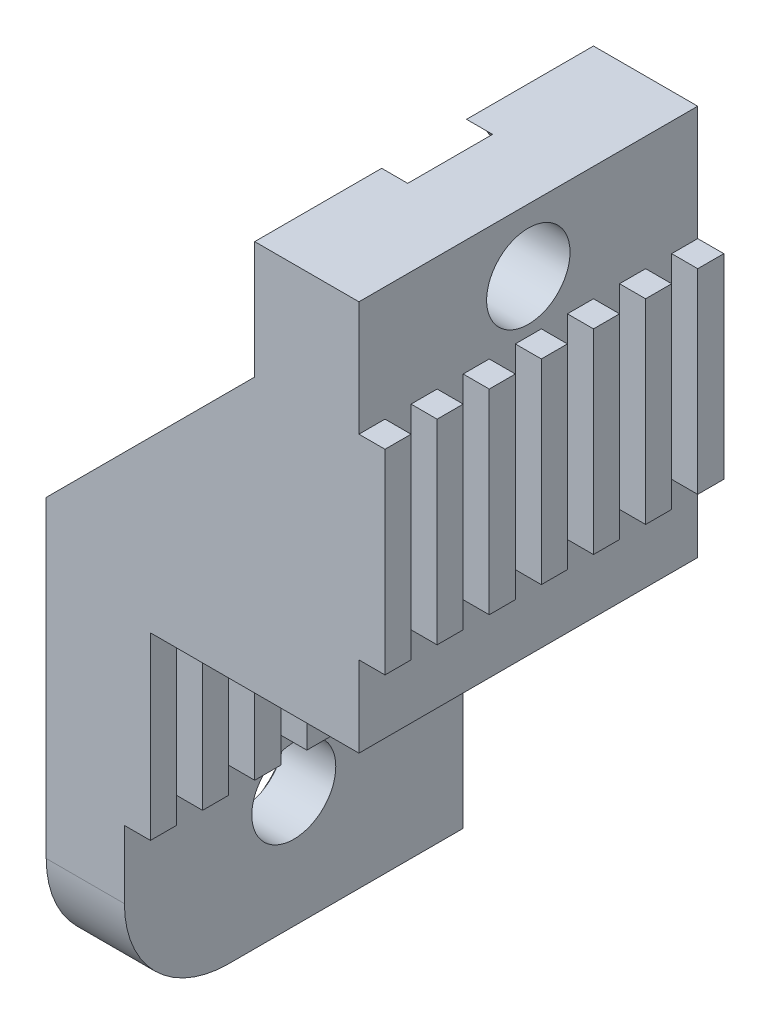
SolidWorks part; units mm, degrees
ref_plane "Front Plane" through (0, 0, 0) normal (0, 0, 1) x (1, 0, 0)
ref_plane "Top Plane" through (0, 0, 0) normal (0, 1, 0) x (1, 0, 0)
ref_plane "Right Plane" through (0, 0, 0) normal (1, 0, 0) x (0, 0, -1)
sketch "Sketch1" plane through (0, 0, 98.1716) normal (0, 0, 1) x (1, 0, 0)
  line L0 (34.2144, 63.2635) -> (28.2644, 63.2635) construction
  line L1 (31.2144, 78.2635) -> (35.2144, 78.2635)
  line L2 (31.2144, 78.2635) -> (31.2144, 63.7635)
  line L4 (35.2144, 78.2635) -> (35.2144, 66.8635)
  line L5 (23.2144, 49.7635) -> (26.2144, 49.7635)
  line L6 (23.2144, 49.7635) -> (23.2144, 63.2635)
  line L8 (26.2144, 49.7635) -> (26.2144, 63.2635)
  line L10 (36.7144, 67.3635) -> (36.7144, 73.8635) construction
  line L12 (31.2144, 63.7635) -> (23.2144, 63.7635)
  line L17 (23.2144, 63.7635) -> (23.2144, 63.2635)
  line L22 (26.2144, 63.2635) -> (35.2144, 63.2635)
  line L24 (35.2144, 66.8635) -> (35.2144, 63.2635)
  dimension "D1" = 14.5
  dimension "D2" = 3
  dimension "D3" = 0
  dimension "D4" = 4
  dimension "D5" = 1.5
  dimension "D6" = 0
  dimension "D7" = 14
  dimension "D8" = 0.5
  dimension "D9" = 5
extrude "Boss-Extrude1" add sketch "Sketch1" against normal blind 13
sketch "Sketch2" plane through (35.2144, 0, 0) normal (1, 0, 0) x (0, 0, -1)
  line L0 (-85.1716, 49.7635) -> (-98.1716, 49.7635) construction
  circle A0 centre (-91.6716, 75.8635) radius 1.6
  circle A1 centre (-91.6716, 54.2635) radius 1.6115
  dimension "D1" = 4.5
extrude "Cut-Extrude1" cut sketch "Sketch2" against normal blind 20
sketch "Sketch3" plane through (23.2144, 0, 0) normal (-1, 0, 0) x (0, 0, 1)
  circle A0 centre (91.6716, 54.2635) radius 3
  dimension "D1" = 6
extrude "Cut-Extrude2" cut sketch "Sketch3" against normal blind 1
sketch "Sketch4" plane through (31.2144, 0, 0) normal (-1, 0, 0) x (0, 0, 1)
  circle A0 centre (91.6716, 75.8635) radius 2.9
  dimension "D1" = 5.8
extrude "Cut-Extrude3" cut sketch "Sketch4" against normal blind 1
sketch "Sketch5" plane through (35.2144, 0, 0) normal (1, 0, 0) x (0, 0, -1)
  line L1 (-98.1716, 66.3635) -> (-97.1716, 66.3635)
  line L2 (-98.1716, 66.3635) -> (-98.1716, 73.8635)
  line L3 (-98.1716, 73.8635) -> (-97.1716, 73.8635)
  line L4 (-97.1716, 66.3635) -> (-97.1716, 73.8635)
  dimension "D1" = 7.5
  dimension "D2" = 1
extrude "Boss-Extrude2" add sketch "Sketch5" along normal blind 1
pattern_linear "LPattern1" count 7 spacing 2 along (0, 0, -1) of "Boss-Extrude2"
sketch "Sketch6" plane through (26.2144, 0, 0) normal (1, 0, 0) x (0, 0, -1)
  line L1 (-98.1716, 63.8635) -> (-97.1716, 63.8635)
  line L2 (-98.1716, 63.8635) -> (-98.1716, 56.3635)
  line L3 (-98.1716, 56.3635) -> (-97.1716, 56.3635)
  line L4 (-97.1716, 63.8635) -> (-97.1716, 56.3635)
  dimension "D1" = 1
  dimension "D2" = 7.5
extrude "Boss-Extrude3" add sketch "Sketch6" along normal blind 1
pattern_linear "LPattern2" count 7 spacing 2 along (0, 0, -1) of "Boss-Extrude3"
chamfer "Chamfer1" distance 10 angle 45 1 edges at (31.2144, 63.7635, 91.6716)
fillet "Fillet1" radius 4 1 edges at (24.7144, 49.7635, 98.1716)
